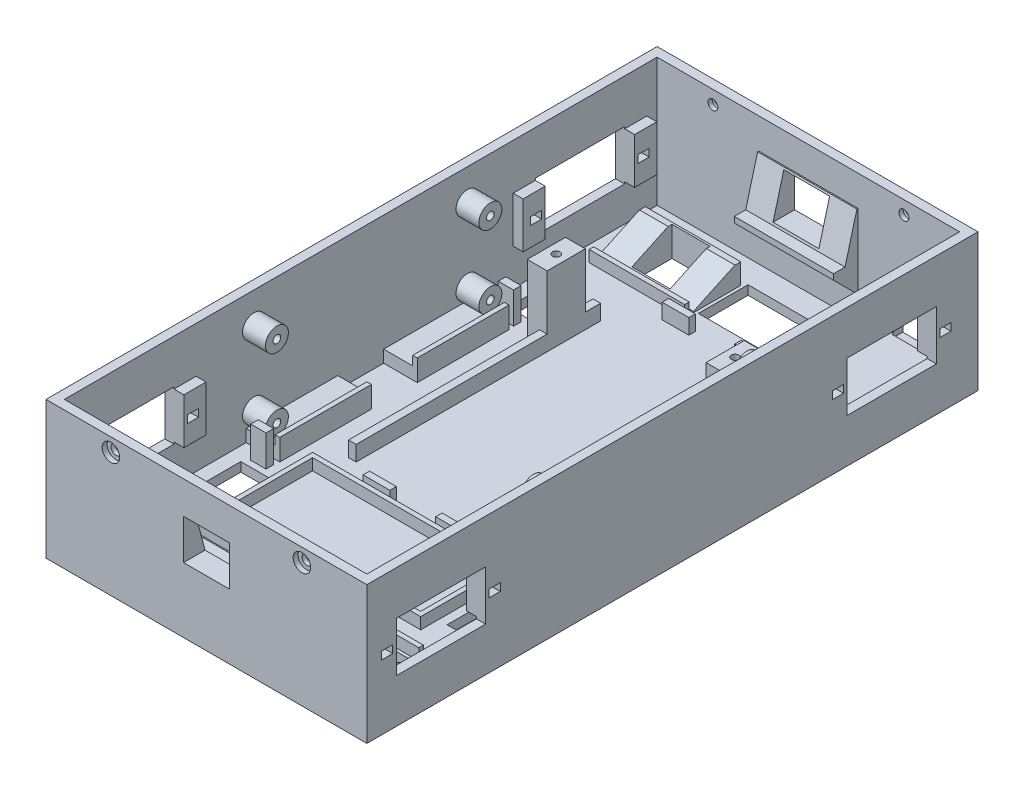
SolidWorks part; units mm, degrees
ref_plane "Front Plane" through (0, 0, 0) normal (0, 0, 1) x (1, 0, 0)
ref_plane "Top Plane" through (0, 0, 0) normal (0, 1, 0) x (1, 0, 0)
ref_plane "Right Plane" through (0, 0, 0) normal (1, 0, 0) x (0, 0, -1)
sketch "Sketch1" plane through (0, 0, 0) normal (0, 0, 1) x (1, 0, 0)
  line L1 (-42, 0) -> (42, 0)
  line L2 (-42, 0) -> (-42, 36)
  line L3 (-42, 36) -> (42, 36)
  line L4 (42, 0) -> (42, 36)
extrude "Boss-Extrude1" add sketch "Sketch1" along normal blind 160 from offset 80 offset against normal yes
sketch "Sketch2" plane through (0, 0, 0) normal (0, 0, 1) x (1, 0, 0)
  line L1 (-39.6, 2.4) -> (39.6, 2.4)
  line L2 (-39.6, 2.4) -> (-39.6, 41)
  line L3 (-39.6, 41) -> (39.6, 41)
  line L4 (39.6, 2.4) -> (39.6, 41)
extrude "Boss-Extrude2" add sketch "Sketch2" along normal blind 155.2 from offset 77.6 separate body offset against normal yes
combine bodies "Combine1" operation type subtract main body 101 bodies to subtract 102
sketch "Sketch3" plane through (0, 0, 0) normal (0, 0, 1) x (1, 0, 0)
  line L1 (-39.6, 12) -> (-37, 12)
  line L2 (-39.6, 12) -> (-39.6, 24)
  line L3 (-39.6, 24) -> (-37, 24)
  line L4 (-37, 12) -> (-37, 24)
extrude "Boss-Extrude3" add sketch "Sketch3" along normal blind 35 from offset 74.9 offset against normal yes
sketch "Sketch4" plane through (0, 0, 0) normal (0, 0, 1) x (1, 0, 0)
  line L1 (-43, 11.5) -> (-35.2, 11.5)
  line L2 (-43, 11.5) -> (-43, 24.5)
  line L3 (-43, 24.5) -> (-35.2, 24.5)
  line L4 (-35.2, 11.5) -> (-35.2, 24.5)
extrude "Boss-Extrude4" add sketch "Sketch4" along normal blind 23.4 from offset 69.1 separate body offset against normal yes
combine bodies "Combine2" operation type subtract main body 104 bodies to subtract 105
sketch "Sketch5" plane through (0, 0, 0) normal (0, 0, 1) x (1, 0, 0)
  line L1 (-43, 17) -> (-35.2, 17)
  line L2 (-43, 17) -> (-43, 19)
  line L3 (-43, 19) -> (-35.2, 19)
  line L4 (-35.2, 17) -> (-35.2, 19)
extrude "Boss-Extrude5" add sketch "Sketch5" along normal blind 2.9 from offset 72.925 separate body offset against normal yes
combine bodies "Combine3" operation type subtract main body 106 bodies to subtract 107
sketch "Sketch6" plane through (0, 0, 0) normal (0, 0, 1) x (1, 0, 0)
  line L1 (-43, 17) -> (-35.2, 17)
  line L2 (-43, 17) -> (-43, 19)
  line L3 (-43, 19) -> (-35.2, 19)
  line L4 (-35.2, 17) -> (-35.2, 19)
extrude "Boss-Extrude6" add sketch "Sketch6" along normal blind 2.9 from offset 44.775 separate body offset against normal yes
combine bodies "Combine4" operation type subtract main body 108 bodies to subtract 109
sketch "Sketch7" plane through (0, 0, 0) normal (0, 0, 1) x (1, 0, 0)
  line L1 (-36, -1) -> (-28, -1)
  line L2 (-36, -1) -> (-36, 3.4)
  line L3 (-36, 3.4) -> (-28, 3.4)
  line L4 (-28, -1) -> (-28, 3.4)
extrude "Boss-Extrude7" add sketch "Sketch7" along normal blind 10 from offset 45 separate body offset against normal yes
combine bodies "Combine5" operation type subtract main body 110 bodies to subtract 111
sketch "Sketch8" plane through (0, 0, 0) normal (0, 0, 1) x (1, 0, 0)
  line L1 (-39.6, 12) -> (-37, 12)
  line L2 (-39.6, 12) -> (-39.6, 24)
  line L3 (-39.6, 24) -> (-37, 24)
  line L4 (-37, 12) -> (-37, 24)
extrude "Boss-Extrude8" add sketch "Sketch8" along normal blind 34.5 from offset 43.1
sketch "Sketch9" plane through (0, 0, 0) normal (0, 0, 1) x (1, 0, 0)
  line L1 (-43, 11.5) -> (-35.2, 11.5)
  line L2 (-43, 11.5) -> (-43, 24.5)
  line L3 (-43, 24.5) -> (-35.2, 24.5)
  line L4 (-35.2, 11.5) -> (-35.2, 24.5)
extrude "Boss-Extrude9" add sketch "Sketch9" along normal blind 23.4 from offset 48.9 separate body
combine bodies "Combine6" operation type subtract main body 113 bodies to subtract 114
sketch "Sketch10" plane through (0, 0, 0) normal (0, 0, 1) x (1, 0, 0)
  line L1 (-43, 17) -> (-35.2, 17)
  line L2 (-43, 17) -> (-43, 19)
  line L3 (-43, 19) -> (-35.2, 19)
  line L4 (-35.2, 17) -> (-35.2, 19)
extrude "Boss-Extrude10" add sketch "Sketch10" along normal blind 2.9 from offset 45.075 separate body
combine bodies "Combine7" operation type subtract main body 115 bodies to subtract 116
sketch "Sketch11" plane through (0, 0, 0) normal (0, 0, 1) x (1, 0, 0)
  line L1 (-43, 17) -> (-35.2, 17)
  line L2 (-43, 17) -> (-43, 19)
  line L3 (-43, 19) -> (-35.2, 19)
  line L4 (-35.2, 17) -> (-35.2, 19)
extrude "Boss-Extrude11" add sketch "Sketch11" along normal blind 2.9 from offset 73.225 separate body
combine bodies "Combine8" operation type subtract main body 117 bodies to subtract 118
sketch "Sketch12" plane through (0, 0, 0) normal (0, 0, 1) x (1, 0, 0)
  line L1 (-36, -1) -> (-28, -1)
  line L2 (-36, -1) -> (-36, 3.4)
  line L3 (-36, 3.4) -> (-28, 3.4)
  line L4 (-28, -1) -> (-28, 3.4)
extrude "Boss-Extrude12" add sketch "Sketch12" along normal blind 10 from offset 35 separate body
combine bodies "Combine9" operation type subtract main body 119 bodies to subtract 120
sketch "Sketch13" plane through (0, 0, 0) normal (1, 0, 0) x (0, 0, -1)
  circle A0 centre (27.94, 8.775) radius 3
extrude "Boss-Extrude13" add sketch "Sketch13" along normal blind 6 from offset 39.6 offset against normal yes
sketch "Sketch14" plane through (0, 0, 0) normal (1, 0, 0) x (0, 0, -1)
  circle A0 centre (27.94, 8.775) radius 1
extrude "Boss-Extrude14" add sketch "Sketch14" along normal blind 7.4 from offset 40.4 separate body offset against normal yes
combine bodies "Combine10" operation type subtract main body 122 bodies to subtract 123
sketch "Sketch15" plane through (0, 0, 0) normal (1, 0, 0) x (0, 0, -1)
  circle A0 centre (27.94, 27.825) radius 3
extrude "Boss-Extrude15" add sketch "Sketch15" along normal blind 6 from offset 39.6 offset against normal yes
sketch "Sketch16" plane through (0, 0, 0) normal (1, 0, 0) x (0, 0, -1)
  circle A0 centre (27.94, 27.825) radius 1
extrude "Boss-Extrude16" add sketch "Sketch16" along normal blind 7.4 from offset 40.4 separate body offset against normal yes
combine bodies "Combine11" operation type subtract main body 125 bodies to subtract 126
sketch "Sketch17" plane through (0, 0, 0) normal (1, 0, 0) x (0, 0, -1)
  circle A0 centre (-27.94, 8.775) radius 3
extrude "Boss-Extrude17" add sketch "Sketch17" along normal blind 6 from offset 39.6 offset against normal yes
sketch "Sketch18" plane through (0, 0, 0) normal (1, 0, 0) x (0, 0, -1)
  circle A0 centre (-27.94, 8.775) radius 1
extrude "Boss-Extrude18" add sketch "Sketch18" along normal blind 7.4 from offset 40.4 separate body offset against normal yes
combine bodies "Combine12" operation type subtract main body 128 bodies to subtract 129
sketch "Sketch19" plane through (0, 0, 0) normal (1, 0, 0) x (0, 0, -1)
  circle A0 centre (-27.94, 27.825) radius 3
extrude "Boss-Extrude19" add sketch "Sketch19" along normal blind 6 from offset 39.6 offset against normal yes
sketch "Sketch20" plane through (0, 0, 0) normal (1, 0, 0) x (0, 0, -1)
  circle A0 centre (-27.94, 27.825) radius 1
extrude "Boss-Extrude20" add sketch "Sketch20" along normal blind 7.4 from offset 40.4 separate body offset against normal yes
combine bodies "Combine13" operation type subtract main body 131 bodies to subtract 132
sketch "Sketch21" plane through (0, 0, 0) normal (0, 0, 1) x (1, 0, 0)
  line L1 (-39.6, 2.4) -> (-32, 2.4)
  line L2 (-39.6, 2.4) -> (-39.6, 5.6)
  line L3 (-39.6, 5.6) -> (-32, 5.6)
  line L4 (-32, 2.4) -> (-32, 5.6)
extrude "Boss-Extrude21" add sketch "Sketch21" along normal blind 24 from offset 30 offset against normal yes
sketch "Sketch22" plane through (0, 0, 0) normal (0, 0, 1) x (1, 0, 0)
  line L1 (-32, 2.4) -> (-30.8, 2.4)
  line L2 (-32, 2.4) -> (-32, 8)
  line L3 (-32, 8) -> (-30.8, 8)
  line L4 (-30.8, 2.4) -> (-30.8, 8)
extrude "Boss-Extrude22" add sketch "Sketch22" along normal blind 24 from offset 30 offset against normal yes
sketch "Sketch23" plane through (0, 0, 0) normal (0, 0, 1) x (1, 0, 0)
  line L1 (-39.6, 2.4) -> (-32, 2.4)
  line L2 (-39.6, 2.4) -> (-39.6, 5.6)
  line L3 (-39.6, 5.6) -> (-32, 5.6)
  line L4 (-32, 2.4) -> (-32, 5.6)
extrude "Boss-Extrude23" add sketch "Sketch23" along normal blind 24 from offset 6
sketch "Sketch24" plane through (0, 0, 0) normal (0, 0, 1) x (1, 0, 0)
  line L1 (-32, 2.4) -> (-30.8, 2.4)
  line L2 (-32, 2.4) -> (-32, 8)
  line L3 (-32, 8) -> (-30.8, 8)
  line L4 (-30.8, 2.4) -> (-30.8, 8)
extrude "Boss-Extrude24" add sketch "Sketch24" along normal blind 24 from offset 6
sketch "Sketch25" plane through (0, 0, 0) normal (0, 0, 1) x (1, 0, 0)
  line L1 (-35, 2.4) -> (-31, 2.4)
  line L2 (-35, 2.4) -> (-35, 10.6)
  line L3 (-35, 10.6) -> (-31, 10.6)
  line L4 (-31, 2.4) -> (-31, 10.6)
extrude "Boss-Extrude25" add sketch "Sketch25" along normal blind 2 from offset 31.4
sketch "Sketch26" plane through (0, 0, 0) normal (0, 0, 1) x (1, 0, 0)
  line L1 (-35, 2.4) -> (-31, 2.4)
  line L2 (-35, 2.4) -> (-35, 10.6)
  line L3 (-35, 10.6) -> (-31, 10.6)
  line L4 (-31, 2.4) -> (-31, 10.6)
extrude "Boss-Extrude26" add sketch "Sketch26" along normal blind 2 from offset 33.4 offset against normal yes
sketch "Sketch27" plane through (0, 0, 0) normal (0, 0, 1) x (1, 0, 0)
  line L1 (-22.8, 2.4) -> (-20.8, 2.4)
  line L2 (-22.8, 2.4) -> (-22.8, 6.4)
  line L3 (-22.8, 6.4) -> (-20.8, 6.4)
  line L4 (-20.8, 2.4) -> (-20.8, 6.4)
extrude "Boss-Extrude27" add sketch "Sketch27" along normal blind 64 from offset 44 offset against normal yes
sketch "Sketch28" plane through (0, 0, 0) normal (0, 0, 1) x (1, 0, 0)
  line L1 (-26, 2.4) -> (-20.8, 2.4)
  line L2 (-26, 2.4) -> (-26, 20.75)
  line L3 (-26, 20.75) -> (-20.8, 20.75)
  line L4 (-20.8, 2.4) -> (-20.8, 20.75)
extrude "Boss-Extrude28" add sketch "Sketch28" along normal blind 10 from offset 40 offset against normal yes
sketch "Sketch29" plane through (0, 0, 0) normal (0, 1, 0) x (1, 0, 0)
  circle A0 centre (-23.4, 35) radius 1
extrude "Boss-Extrude29" add sketch "Sketch29" along normal blind 13.75 from offset 8 separate body
combine bodies "Combine14" operation type subtract main body 141 bodies to subtract 142
sketch "Sketch30" plane through (0, 0, 0) normal (0, 0, 1) x (1, 0, 0)
  line L1 (-25.7, 2.4) -> (-24.5, 2.4)
  line L2 (-25.7, 2.4) -> (-25.7, 5.4)
  line L3 (-25.7, 5.4) -> (-24.5, 5.4)
  line L4 (-24.5, 2.4) -> (-24.5, 5.4)
extrude "Boss-Extrude30" add sketch "Sketch30" along normal blind 20.7 from offset 27.7
sketch "Sketch31" plane through (0, 0, 0) normal (0, 0, 1) x (1, 0, 0)
  line L1 (37, 12) -> (39.6, 12)
  line L2 (37, 12) -> (37, 24)
  line L3 (37, 24) -> (39.6, 24)
  line L4 (39.6, 12) -> (39.6, 24)
extrude "Boss-Extrude31" add sketch "Sketch31" along normal blind 35 from offset 74.9 offset against normal yes
sketch "Sketch32" plane through (0, 0, 0) normal (0, 0, 1) x (1, 0, 0)
  line L1 (35.2, 11.5) -> (43, 11.5)
  line L2 (35.2, 11.5) -> (35.2, 24.5)
  line L3 (35.2, 24.5) -> (43, 24.5)
  line L4 (43, 11.5) -> (43, 24.5)
extrude "Boss-Extrude32" add sketch "Sketch32" along normal blind 23.4 from offset 69.1 separate body offset against normal yes
combine bodies "Combine15" operation type subtract main body 145 bodies to subtract 146
sketch "Sketch33" plane through (0, 0, 0) normal (0, 0, 1) x (1, 0, 0)
  line L1 (35.2, 17) -> (43, 17)
  line L2 (35.2, 17) -> (35.2, 19)
  line L3 (35.2, 19) -> (43, 19)
  line L4 (43, 17) -> (43, 19)
extrude "Boss-Extrude33" add sketch "Sketch33" along normal blind 2.9 from offset 72.925 separate body offset against normal yes
combine bodies "Combine16" operation type subtract main body 147 bodies to subtract 148
sketch "Sketch34" plane through (0, 0, 0) normal (0, 0, 1) x (1, 0, 0)
  line L1 (35.2, 17) -> (43, 17)
  line L2 (35.2, 17) -> (35.2, 19)
  line L3 (35.2, 19) -> (43, 19)
  line L4 (43, 17) -> (43, 19)
extrude "Boss-Extrude34" add sketch "Sketch34" along normal blind 2.9 from offset 44.775 separate body offset against normal yes
combine bodies "Combine17" operation type subtract main body 149 bodies to subtract 150
sketch "Sketch35" plane through (0, 0, 0) normal (0, 0, 1) x (1, 0, 0)
  line L1 (28, -1) -> (36, -1)
  line L2 (28, -1) -> (28, 3.4)
  line L3 (28, 3.4) -> (36, 3.4)
  line L4 (36, -1) -> (36, 3.4)
extrude "Boss-Extrude35" add sketch "Sketch35" along normal blind 10 from offset 45 separate body offset against normal yes
combine bodies "Combine18" operation type subtract main body 151 bodies to subtract 152
sketch "Sketch36" plane through (0, 0, 0) normal (0, 0, 1) x (1, 0, 0)
  line L1 (37, 12) -> (39.6, 12)
  line L2 (37, 12) -> (37, 24)
  line L3 (37, 24) -> (39.6, 24)
  line L4 (39.6, 12) -> (39.6, 24)
extrude "Boss-Extrude36" add sketch "Sketch36" along normal blind 34.5 from offset 43.1
sketch "Sketch37" plane through (0, 0, 0) normal (0, 0, 1) x (1, 0, 0)
  line L1 (35.2, 11.5) -> (43, 11.5)
  line L2 (35.2, 11.5) -> (35.2, 24.5)
  line L3 (35.2, 24.5) -> (43, 24.5)
  line L4 (43, 11.5) -> (43, 24.5)
extrude "Boss-Extrude37" add sketch "Sketch37" along normal blind 23.4 from offset 48.9 separate body
combine bodies "Combine19" operation type subtract main body 154 bodies to subtract 155
sketch "Sketch38" plane through (0, 0, 0) normal (0, 0, 1) x (1, 0, 0)
  line L1 (35.2, 17) -> (43, 17)
  line L2 (35.2, 17) -> (35.2, 19)
  line L3 (35.2, 19) -> (43, 19)
  line L4 (43, 17) -> (43, 19)
extrude "Boss-Extrude38" add sketch "Sketch38" along normal blind 2.9 from offset 45.075 separate body
combine bodies "Combine20" operation type subtract main body 156 bodies to subtract 157
sketch "Sketch39" plane through (0, 0, 0) normal (0, 0, 1) x (1, 0, 0)
  line L1 (35.2, 17) -> (43, 17)
  line L2 (35.2, 17) -> (35.2, 19)
  line L3 (35.2, 19) -> (43, 19)
  line L4 (43, 17) -> (43, 19)
extrude "Boss-Extrude39" add sketch "Sketch39" along normal blind 2.9 from offset 73.225 separate body
combine bodies "Combine21" operation type subtract main body 158 bodies to subtract 159
sketch "Sketch40" plane through (0, 0, 0) normal (0, 0, 1) x (1, 0, 0)
  line L1 (28, -1) -> (36, -1)
  line L2 (28, -1) -> (28, 3.4)
  line L3 (28, 3.4) -> (36, 3.4)
  line L4 (36, -1) -> (36, 3.4)
extrude "Boss-Extrude40" add sketch "Sketch40" along normal blind 10 from offset 35 separate body
combine bodies "Combine22" operation type subtract main body 160 bodies to subtract 161
sketch "Sketch41" plane through (0, 0, 0) normal (1, 0, 0) x (0, 0, -1)
  circle A0 centre (27.94, 8.775) radius 3
extrude "Boss-Extrude41" add sketch "Sketch41" along normal blind 6 from offset 33.6
sketch "Sketch42" plane through (0, 0, 0) normal (1, 0, 0) x (0, 0, -1)
  circle A0 centre (27.94, 8.775) radius 1
extrude "Boss-Extrude42" add sketch "Sketch42" along normal blind 7.4 from offset 33 separate body
combine bodies "Combine23" operation type subtract main body 163 bodies to subtract 164
sketch "Sketch43" plane through (0, 0, 0) normal (1, 0, 0) x (0, 0, -1)
  circle A0 centre (27.94, 27.825) radius 3
extrude "Boss-Extrude43" add sketch "Sketch43" along normal blind 6 from offset 33.6
sketch "Sketch44" plane through (0, 0, 0) normal (1, 0, 0) x (0, 0, -1)
  circle A0 centre (27.94, 27.825) radius 1
extrude "Boss-Extrude44" add sketch "Sketch44" along normal blind 7.4 from offset 33 separate body
combine bodies "Combine24" operation type subtract main body 166 bodies to subtract 167
sketch "Sketch45" plane through (0, 0, 0) normal (1, 0, 0) x (0, 0, -1)
  circle A0 centre (-27.94, 8.775) radius 3
extrude "Boss-Extrude45" add sketch "Sketch45" along normal blind 6 from offset 33.6
sketch "Sketch46" plane through (0, 0, 0) normal (1, 0, 0) x (0, 0, -1)
  circle A0 centre (-27.94, 8.775) radius 1
extrude "Boss-Extrude46" add sketch "Sketch46" along normal blind 7.4 from offset 33 separate body
combine bodies "Combine25" operation type subtract main body 169 bodies to subtract 170
sketch "Sketch47" plane through (0, 0, 0) normal (1, 0, 0) x (0, 0, -1)
  circle A0 centre (-27.94, 27.825) radius 3
extrude "Boss-Extrude47" add sketch "Sketch47" along normal blind 6 from offset 33.6
sketch "Sketch48" plane through (0, 0, 0) normal (1, 0, 0) x (0, 0, -1)
  circle A0 centre (-27.94, 27.825) radius 1
extrude "Boss-Extrude48" add sketch "Sketch48" along normal blind 7.4 from offset 33 separate body
combine bodies "Combine26" operation type subtract main body 172 bodies to subtract 173
sketch "Sketch49" plane through (0, 0, 0) normal (0, 0, 1) x (1, 0, 0)
  line L1 (32, 2.4) -> (39.6, 2.4)
  line L2 (32, 2.4) -> (32, 5.6)
  line L3 (32, 5.6) -> (39.6, 5.6)
  line L4 (39.6, 2.4) -> (39.6, 5.6)
extrude "Boss-Extrude49" add sketch "Sketch49" along normal blind 24 from offset 30 offset against normal yes
sketch "Sketch50" plane through (0, 0, 0) normal (0, 0, 1) x (1, 0, 0)
  line L1 (30.8, 2.4) -> (32, 2.4)
  line L2 (30.8, 2.4) -> (30.8, 8)
  line L3 (30.8, 8) -> (32, 8)
  line L4 (32, 2.4) -> (32, 8)
extrude "Boss-Extrude50" add sketch "Sketch50" along normal blind 24 from offset 30 offset against normal yes
sketch "Sketch51" plane through (0, 0, 0) normal (0, 0, 1) x (1, 0, 0)
  line L1 (32, 2.4) -> (39.6, 2.4)
  line L2 (32, 2.4) -> (32, 5.6)
  line L3 (32, 5.6) -> (39.6, 5.6)
  line L4 (39.6, 2.4) -> (39.6, 5.6)
extrude "Boss-Extrude51" add sketch "Sketch51" along normal blind 24 from offset 6
sketch "Sketch52" plane through (0, 0, 0) normal (0, 0, 1) x (1, 0, 0)
  line L1 (30.8, 2.4) -> (32, 2.4)
  line L2 (30.8, 2.4) -> (30.8, 8)
  line L3 (30.8, 8) -> (32, 8)
  line L4 (32, 2.4) -> (32, 8)
extrude "Boss-Extrude52" add sketch "Sketch52" along normal blind 24 from offset 6
sketch "Sketch53" plane through (0, 0, 0) normal (0, 0, 1) x (1, 0, 0)
  line L1 (31, 2.4) -> (35, 2.4)
  line L2 (31, 2.4) -> (31, 10.6)
  line L3 (31, 10.6) -> (35, 10.6)
  line L4 (35, 2.4) -> (35, 10.6)
extrude "Boss-Extrude53" add sketch "Sketch53" along normal blind 2 from offset 31.4
sketch "Sketch54" plane through (0, 0, 0) normal (0, 0, 1) x (1, 0, 0)
  line L1 (31, 2.4) -> (35, 2.4)
  line L2 (31, 2.4) -> (31, 10.6)
  line L3 (31, 10.6) -> (35, 10.6)
  line L4 (35, 2.4) -> (35, 10.6)
extrude "Boss-Extrude54" add sketch "Sketch54" along normal blind 2 from offset 33.4 offset against normal yes
sketch "Sketch55" plane through (0, 0, 0) normal (0, 0, 1) x (1, 0, 0)
  line L1 (20.8, 2.4) -> (22.8, 2.4)
  line L2 (20.8, 2.4) -> (20.8, 6.4)
  line L3 (20.8, 6.4) -> (22.8, 6.4)
  line L4 (22.8, 2.4) -> (22.8, 6.4)
extrude "Boss-Extrude55" add sketch "Sketch55" along normal blind 64 from offset 44 offset against normal yes
sketch "Sketch56" plane through (0, 0, 0) normal (0, 0, 1) x (1, 0, 0)
  line L1 (20.8, 2.4) -> (26, 2.4)
  line L2 (20.8, 2.4) -> (20.8, 20.75)
  line L3 (20.8, 20.75) -> (26, 20.75)
  line L4 (26, 2.4) -> (26, 20.75)
extrude "Boss-Extrude56" add sketch "Sketch56" along normal blind 10 from offset 40 offset against normal yes
sketch "Sketch57" plane through (0, 0, 0) normal (0, 1, 0) x (1, 0, 0)
  circle A0 centre (23.4, 35) radius 1
extrude "Boss-Extrude57" add sketch "Sketch57" along normal blind 13.75 from offset 8 separate body
combine bodies "Combine27" operation type subtract main body 182 bodies to subtract 183
sketch "Sketch58" plane through (0, 0, 0) normal (0, 0, 1) x (1, 0, 0)
  line L1 (24.5, 2.4) -> (25.7, 2.4)
  line L2 (24.5, 2.4) -> (24.5, 5.4)
  line L3 (24.5, 5.4) -> (25.7, 5.4)
  line L4 (25.7, 2.4) -> (25.7, 5.4)
extrude "Boss-Extrude58" add sketch "Sketch58" along normal blind 20.7 from offset 27.7
sketch "Sketch59" plane through (0, 0, 0) normal (0, 0, 1) x (1, 0, 0)
  line L1 (-25.7, 2.4) -> (25.7, 2.4)
  line L2 (-25.7, 2.4) -> (-25.7, 5.4)
  line L3 (-25.7, 5.4) -> (25.7, 5.4)
  line L4 (25.7, 2.4) -> (25.7, 5.4)
extrude "Boss-Extrude59" add sketch "Sketch59" along normal blind 1.2 from offset 26.5
sketch "Sketch60" plane through (0, 0, 0) normal (0, 0, 1) x (1, 0, 0)
  line L1 (-25.7, 2.4) -> (25.7, 2.4)
  line L2 (-25.7, 2.4) -> (-25.7, 5.4)
  line L3 (-25.7, 5.4) -> (25.7, 5.4)
  line L4 (25.7, 2.4) -> (25.7, 5.4)
extrude "Boss-Extrude60" add sketch "Sketch60" along normal blind 1.2 from offset 48.4
sketch "Sketch61" plane through (0, 0, 0) normal (0, 0, 1) x (1, 0, 0)
  line L1 (-13, 2.4) -> (-6, 2.4)
  line L2 (-13, 2.4) -> (-13, 6.4)
  line L3 (-13, 6.4) -> (-6, 6.4)
  line L4 (-6, 2.4) -> (-6, 6.4)
extrude "Boss-Extrude61" add sketch "Sketch61" along normal blind 1.7 from offset 54 offset against normal yes
sketch "Sketch62" plane through (0, 0, 0) normal (0, 0, 1) x (1, 0, 0)
  line L1 (6, 2.4) -> (13, 2.4)
  line L2 (6, 2.4) -> (6, 6.4)
  line L3 (6, 6.4) -> (13, 6.4)
  line L4 (13, 2.4) -> (13, 6.4)
extrude "Boss-Extrude62" add sketch "Sketch62" along normal blind 1.7 from offset 54 offset against normal yes
sketch "Sketch63" plane through (0, 0, 0) normal (0, 0, 1) x (1, 0, 0)
  line L1 (-13, 2.4) -> (-6, 2.4)
  line L2 (-13, 2.4) -> (-13, 6.4)
  line L3 (-13, 6.4) -> (-6, 6.4)
  line L4 (-6, 2.4) -> (-6, 6.4)
extrude "Boss-Extrude63" add sketch "Sketch63" along normal blind 1.7 from offset 24.3
sketch "Sketch64" plane through (0, 0, 0) normal (0, 0, 1) x (1, 0, 0)
  line L1 (6, 2.4) -> (13, 2.4)
  line L2 (6, 2.4) -> (6, 6.4)
  line L3 (6, 6.4) -> (13, 6.4)
  line L4 (13, 2.4) -> (13, 6.4)
extrude "Boss-Extrude64" add sketch "Sketch64" along normal blind 1.7 from offset 24.3
sketch "Sketch65" plane through (0, 0, 0) normal (1, 0, 0) x (0, 0, -1)
  line L0 (-58, 2.4) -> (-58, 2.7)
  line L1 (-58, 2.7) -> (-68.8757, 7.7714)
  line L2 (-68.8757, 7.7714) -> (-70.3757, 7.7714)
  line L3 (-70.3757, 7.7714) -> (-70.3757, 2.4)
  line L4 (-70.3757, 2.4) -> (-58, 2.4)
extrude "Boss-Extrude65" add sketch "Sketch65" along normal blind 25 from offset 32.5 offset against normal yes
sketch "Sketch66" plane through (0, 0, 0) normal (0, 0, 1) x (1, 0, 0)
  line L1 (-32.5, 2.4) -> (-7.5, 2.4)
  line L2 (-32.5, 2.4) -> (-32.5, 5.4)
  line L3 (-32.5, 5.4) -> (-7.5, 5.4)
  line L4 (-7.5, 2.4) -> (-7.5, 5.4)
extrude "Boss-Extrude66" add sketch "Sketch66" along normal blind 1.2 from offset 55.7
sketch "Sketch67" plane through (0, 0, 0) normal (0, 0, 1) x (1, 0, 0)
  line L1 (-25, -1) -> (-15, -1)
  line L2 (-25, -1) -> (-25, 8.7714)
  line L3 (-25, 8.7714) -> (-15, 8.7714)
  line L4 (-15, -1) -> (-15, 8.7714)
extrude "Boss-Extrude67" add sketch "Sketch67" along normal blind 10.4757 from offset 59.4 separate body
combine bodies "Combine28" operation type subtract main body 193 bodies to subtract 194
sketch "Sketch68" plane through (0, 0, 0) normal (1, 0, 0) x (0, 0, -1)
  line L0 (-58, 2.4) -> (-58, 2.7)
  line L1 (-58, 2.7) -> (-68.8757, 7.7714)
  line L2 (-68.8757, 7.7714) -> (-70.3757, 7.7714)
  line L3 (-70.3757, 7.7714) -> (-70.3757, 2.4)
  line L4 (-70.3757, 2.4) -> (-58, 2.4)
extrude "Boss-Extrude68" add sketch "Sketch68" along normal blind 25 from offset 7.5
sketch "Sketch69" plane through (0, 0, 0) normal (0, 0, 1) x (1, 0, 0)
  line L1 (7.5, 2.4) -> (32.5, 2.4)
  line L2 (7.5, 2.4) -> (7.5, 5.4)
  line L3 (7.5, 5.4) -> (32.5, 5.4)
  line L4 (32.5, 2.4) -> (32.5, 5.4)
extrude "Boss-Extrude69" add sketch "Sketch69" along normal blind 1.2 from offset 55.7
sketch "Sketch70" plane through (0, 0, 0) normal (0, 0, 1) x (1, 0, 0)
  line L1 (15, -1) -> (25, -1)
  line L2 (15, -1) -> (15, 8.7714)
  line L3 (15, 8.7714) -> (25, 8.7714)
  line L4 (25, -1) -> (25, 8.7714)
extrude "Boss-Extrude70" add sketch "Sketch70" along normal blind 10.4757 from offset 59.4 separate body
combine bodies "Combine29" operation type subtract main body 197 bodies to subtract 198
sketch "Sketch71" plane through (0, 0, 0) normal (1, 0, 0) x (0, 0, -1)
  line L0 (58, 2.4) -> (58, 2.7)
  line L1 (58, 2.7) -> (68.8757, 7.7714)
  line L2 (68.8757, 7.7714) -> (70.3757, 7.7714)
  line L3 (70.3757, 7.7714) -> (70.3757, 2.4)
  line L4 (70.3757, 2.4) -> (58, 2.4)
extrude "Boss-Extrude71" add sketch "Sketch71" along normal blind 25 from offset 35.5 offset against normal yes
sketch "Sketch72" plane through (0, 0, 0) normal (0, 0, 1) x (1, 0, 0)
  line L1 (-35.5, 2.4) -> (-10.5, 2.4)
  line L2 (-35.5, 2.4) -> (-35.5, 5.4)
  line L3 (-35.5, 5.4) -> (-10.5, 5.4)
  line L4 (-10.5, 2.4) -> (-10.5, 5.4)
extrude "Boss-Extrude72" add sketch "Sketch72" along normal blind 1.2 from offset 56.9 offset against normal yes
sketch "Sketch73" plane through (0, 0, 0) normal (0, 0, 1) x (1, 0, 0)
  line L1 (-28, -1) -> (-18, -1)
  line L2 (-28, -1) -> (-28, 8.7714)
  line L3 (-28, 8.7714) -> (-18, 8.7714)
  line L4 (-18, -1) -> (-18, 8.7714)
extrude "Boss-Extrude73" add sketch "Sketch73" along normal blind 10.4757 from offset 69.8757 separate body offset against normal yes
combine bodies "Combine30" operation type subtract main body 201 bodies to subtract 202
sketch "Sketch74" plane through (0, 0, 0) normal (1, 0, 0) x (0, 0, -1)
  line L0 (77.6, 8.5) -> (71.2, 14.9)
  line L1 (71.2, 14.9) -> (71.2, 16.4)
  line L2 (71.2, 16.4) -> (74.19, 16.4)
  line L3 (74.19, 16.4) -> (77.3, 28)
  line L4 (77.3, 28) -> (77.6, 28)
  line L5 (77.6, 28) -> (77.6, 8.5)
extrude "Boss-Extrude74" add sketch "Sketch74" along normal blind 26 from offset 13 offset against normal yes
sketch "Sketch75" plane through (0, 0, 0) normal (0, 0, 1) x (1, 0, 0)
  line L1 (-6, 17) -> (6, 17)
  line L2 (-6, 17) -> (-6, 27.5)
  line L3 (-6, 27.5) -> (6, 27.5)
  line L4 (6, 17) -> (6, 27.5)
extrude "Boss-Extrude75" add sketch "Sketch75" along normal blind 7 from offset 81 separate body offset against normal yes
combine bodies "Combine31" operation type subtract main body 204 bodies to subtract 205
sketch "Sketch76" plane through (0, 0, 0) normal (1, 0, 0) x (0, 0, -1)
  line L0 (-77.6, 8.5) -> (-71.2, 14.9)
  line L1 (-71.2, 14.9) -> (-71.2, 16.4)
  line L2 (-71.2, 16.4) -> (-74.19, 16.4)
  line L3 (-74.19, 16.4) -> (-77.3, 28)
  line L4 (-77.3, 28) -> (-77.6, 28)
  line L5 (-77.6, 28) -> (-77.6, 8.5)
extrude "Boss-Extrude76" add sketch "Sketch76" along normal blind 26 from offset 13 offset against normal yes
sketch "Sketch77" plane through (0, 0, 0) normal (0, 0, 1) x (1, 0, 0)
  line L1 (-6, 17) -> (6, 17)
  line L2 (-6, 17) -> (-6, 27.5)
  line L3 (-6, 27.5) -> (6, 27.5)
  line L4 (6, 17) -> (6, 27.5)
extrude "Boss-Extrude77" add sketch "Sketch77" along normal blind 7 from offset 74 separate body
combine bodies "Combine32" operation type subtract main body 207 bodies to subtract 208
sketch "Sketch78" plane through (0, 0, 0) normal (0, 0, 1) x (1, 0, 0)
  line L1 (-9.7, -1) -> (9.7, -1)
  line L2 (-9.7, -1) -> (-9.7, 3.4)
  line L3 (-9.7, 3.4) -> (9.7, 3.4)
  line L4 (9.7, -1) -> (9.7, 3.4)
extrude "Boss-Extrude78" add sketch "Sketch78" along normal blind 13 from offset 71.5 separate body offset against normal yes
combine bodies "Combine33" operation type subtract main body 209 bodies to subtract 210
sketch "Sketch79" plane through (0, 0, 0) normal (0, 0, 1) x (1, 0, 0)
  line L1 (21.3, 2.4) -> (39.3, 2.4)
  line L2 (21.3, 2.4) -> (21.3, 4.4)
  line L3 (21.3, 4.4) -> (39.3, 4.4)
  line L4 (39.3, 2.4) -> (39.3, 4.4)
extrude "Boss-Extrude79" add sketch "Sketch79" along normal blind 31 from offset 77.6 offset against normal yes
sketch "Sketch80" plane through (0, 0, 0) normal (0, 0, 1) x (1, 0, 0)
  line L1 (19.5, 2.4) -> (21.3, 2.4)
  line L2 (19.5, 2.4) -> (19.5, 7.4)
  line L3 (19.5, 7.4) -> (21.3, 7.4)
  line L4 (21.3, 2.4) -> (21.3, 7.4)
extrude "Boss-Extrude80" add sketch "Sketch80" along normal blind 22 from offset 75 offset against normal yes
sketch "Sketch81" plane through (0, 0, 0) normal (0, 0, 1) x (1, 0, 0)
  line L1 (21.3, 2.4) -> (39.6, 2.4)
  line L2 (21.3, 2.4) -> (21.3, 7.4)
  line L3 (21.3, 7.4) -> (39.6, 7.4)
  line L4 (39.6, 2.4) -> (39.6, 7.4)
extrude "Boss-Extrude81" add sketch "Sketch81" along normal blind 1.2 from offset 46.4 offset against normal yes
sketch "Sketch82" plane through (0, 0, 0) normal (0, 0, 1) x (1, 0, 0)
  line L1 (22.3, 3.4) -> (38.3, 3.4)
  line L2 (22.3, 3.4) -> (22.3, 12.4)
  line L3 (22.3, 12.4) -> (38.3, 12.4)
  line L4 (38.3, 3.4) -> (38.3, 12.4)
extrude "Boss-Extrude82" add sketch "Sketch82" along normal blind 3.9 from offset 81 separate body offset against normal yes
combine bodies "Combine34" operation type subtract main body 214 bodies to subtract 215
sketch "Sketch83" plane through (0, 0, 0) normal (0, 0, 1) x (1, 0, 0)
  circle A0 centre (-25, 32.5) radius 1.3
extrude "Boss-Extrude83" add sketch "Sketch83" along normal blind 4.4 from offset 81 separate body offset against normal yes
combine bodies "Combine35" operation type subtract main body 216 bodies to subtract 217
sketch "Sketch84" plane through (0, 0, 0) normal (0, 0, 1) x (1, 0, 0)
  circle A0 centre (-25, 32.5) radius 2.3
extrude "Boss-Extrude84" add sketch "Sketch84" along normal blind 2.3 from offset 81 separate body offset against normal yes
combine bodies "Combine36" operation type subtract main body 218 bodies to subtract 219
sketch "Sketch85" plane through (0, 0, 0) normal (0, 0, 1) x (1, 0, 0)
  circle A0 centre (25, 32.5) radius 1.3
extrude "Boss-Extrude85" add sketch "Sketch85" along normal blind 4.4 from offset 81 separate body offset against normal yes
combine bodies "Combine37" operation type subtract main body 220 bodies to subtract 221
sketch "Sketch86" plane through (0, 0, 0) normal (0, 0, 1) x (1, 0, 0)
  circle A0 centre (25, 32.5) radius 2.3
extrude "Boss-Extrude86" add sketch "Sketch86" along normal blind 2.3 from offset 81 separate body offset against normal yes
combine bodies "Combine38" operation type subtract main body 222 bodies to subtract 223
sketch "Sketch87" plane through (0, 0, 0) normal (0, 0, 1) x (1, 0, 0)
  circle A0 centre (-25, 32.5) radius 1.3
extrude "Boss-Extrude87" add sketch "Sketch87" along normal blind 4.4 from offset 76.6 separate body
combine bodies "Combine39" operation type subtract main body 224 bodies to subtract 225
sketch "Sketch88" plane through (0, 0, 0) normal (0, 0, 1) x (1, 0, 0)
  circle A0 centre (-25, 32.5) radius 2.3
extrude "Boss-Extrude88" add sketch "Sketch88" along normal blind 2.3 from offset 78.7 separate body
combine bodies "Combine40" operation type subtract main body 226 bodies to subtract 227
sketch "Sketch89" plane through (0, 0, 0) normal (0, 0, 1) x (1, 0, 0)
  circle A0 centre (25, 32.5) radius 1.3
extrude "Boss-Extrude89" add sketch "Sketch89" along normal blind 4.4 from offset 76.6 separate body
combine bodies "Combine41" operation type subtract main body 228 bodies to subtract 229
sketch "Sketch90" plane through (0, 0, 0) normal (0, 0, 1) x (1, 0, 0)
  circle A0 centre (25, 32.5) radius 2.3
extrude "Boss-Extrude90" add sketch "Sketch90" along normal blind 2.3 from offset 78.7 separate body
combine bodies "Combine42" operation type subtract main body 230 bodies to subtract 231
